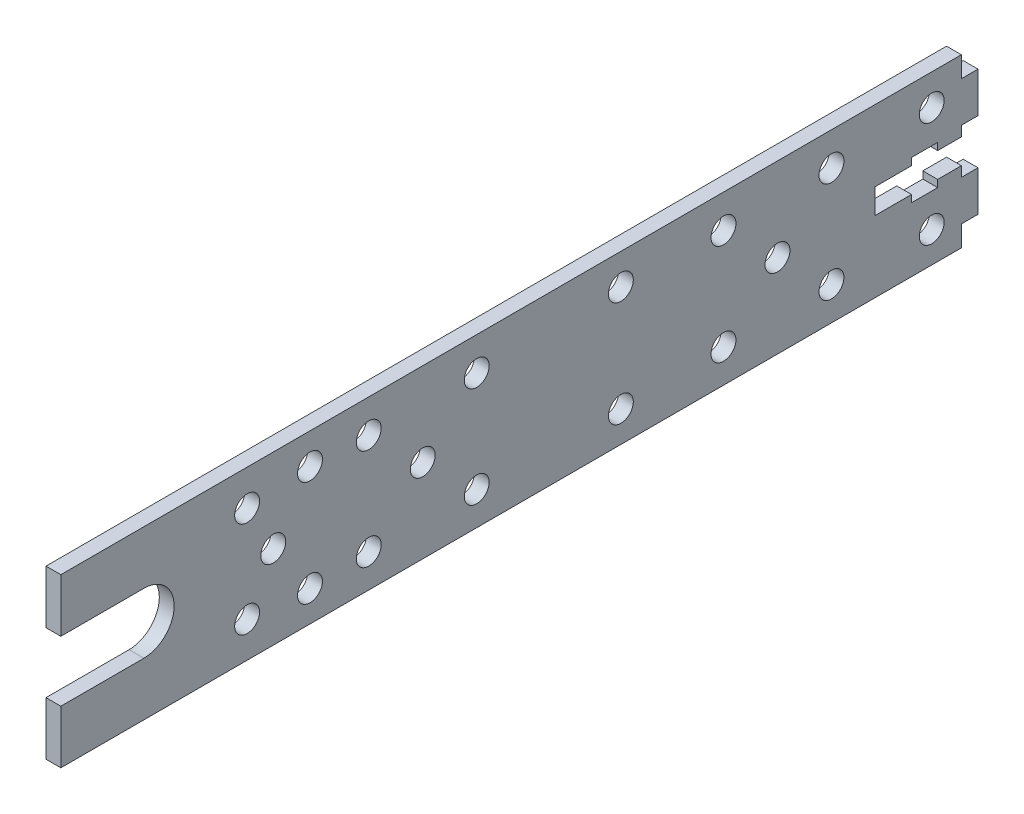
SolidWorks part; units mm, degrees
ref_plane "Front Plane" through (0, 0, 0) normal (0, 0, 1) x (1, 0, 0)
ref_plane "Top Plane" through (0, 0, 0) normal (0, 1, 0) x (1, 0, 0)
ref_plane "Right Plane" through (0, 0, 0) normal (1, 0, 0) x (0, 0, -1)
sketch "Sketch1" plane through (0, 0, 0) normal (1, 0, 0) x (0, 0, -1)
  line L0 (-98.171, 0) -> (98.171, 0) construction
  line L1 (-98.171, 17.907) -> (94.615, 17.907)
  line L2 (-98.171, 17.907) -> (-98.171, 6.477)
  line L3 (-98.171, -17.907) -> (94.615, -17.907)
  line L4 (98.171, 13.462) -> (98.171, 4.826)
  line L5 (94.615, 4.826) -> (94.615, 2.667)
  line L6 (94.615, -2.667) -> (94.615, -4.826)
  line L7 (94.615, 2.667) -> (89.535, 2.667)
  line L8 (94.615, 17.907) -> (94.615, 13.462)
  line L9 (94.615, -2.667) -> (89.535, -2.667)
  line L10 (76.073, 2.667) -> (76.073, -2.667)
  line L11 (86.741, 4.191) -> (86.741, -4.191) construction
  line L12 (-32.258, 10.795) -> (-9.144, 10.795) construction
  line L13 (83.947, 2.667) -> (76.073, 2.667)
  line L14 (89.535, 4.191) -> (83.947, 4.191)
  line L15 (89.535, 4.191) -> (89.535, 2.667)
  line L16 (89.535, -4.191) -> (83.947, -4.191)
  line L17 (83.947, 4.191) -> (83.947, 2.667)
  line L18 (66.802, 10.795) -> (43.688, 10.795) construction
  line L19 (66.802, -10.795) -> (43.688, -10.795) construction
  line L20 (83.947, -2.667) -> (76.073, -2.667)
  line L21 (89.535, -2.667) -> (89.535, -4.191)
  line L22 (83.947, -2.667) -> (83.947, -4.191)
  line L23 (98.171, -4.826) -> (98.171, -13.462)
  line L24 (98.171, 13.462) -> (94.615, 13.462)
  line L25 (98.171, 13.462) -> (98.171, 4.826)
  line L26 (98.171, 4.826) -> (94.615, 4.826)
  line L27 (-32.258, -10.795) -> (-9.144, -10.795) construction
  line L28 (98.171, 13.462) -> (94.615, 4.826) construction
  line L29 (98.171, 4.826) -> (94.615, 13.462) construction
  line L30 (-80.391, 6.477) -> (-98.171, 6.477)
  line L31 (98.171, -4.826) -> (94.615, -4.826)
  line L32 (-20.701, 10.795) -> (-20.701, -10.795) construction
  line L33 (98.171, -13.462) -> (94.615, -4.826) construction
  line L34 (98.171, -4.826) -> (94.615, -13.462) construction
  line L35 (98.171, -13.462) -> (94.615, -13.462)
  line L36 (-80.391, -6.477) -> (-98.171, -6.477)
  line L37 (-98.171, -6.477) -> (-98.171, -17.907)
  line L38 (94.615, -13.462) -> (94.615, -17.907)
  line L39 (55.245, 10.795) -> (55.245, -10.795) construction
  arc A0 (-80.391, -6.477) -> (-80.391, 6.477) centre (-80.391, 0) ccw
  circle A1 centre (-58.293, 10.287) radius 2.667
  circle A2 centre (-58.293, -10.287) radius 2.667
  circle A3 centre (-52.705, 0) radius 2.667
  circle A4 centre (-44.831, 11.303) radius 2.667
  circle A5 centre (21.717, 11.303) radius 2.667
  circle A6 centre (88.265, 11.303) radius 2.667
  circle A7 centre (88.265, -11.303) radius 2.667
  circle A8 centre (21.717, -11.303) radius 2.667
  circle A9 centre (-44.831, -11.303) radius 2.667
  circle A10 centre (-9.144, 10.795) radius 2.667
  circle A11 centre (-32.258, 10.795) radius 2.667
  circle A12 centre (66.802, 10.795) radius 2.667
  circle A13 centre (43.688, 10.795) radius 2.667
  circle A14 centre (43.688, -10.795) radius 2.667
  circle A15 centre (66.802, -10.795) radius 2.667
  circle A16 centre (-32.258, -10.795) radius 2.667
  circle A17 centre (-9.144, -10.795) radius 2.667
  circle A18 centre (-20.701, 0) radius 2.667
  circle A19 centre (55.245, 0) radius 2.667
  point P0 (0, 0)
  point P1 (86.741, 0)
  point P4 (0, 0)
  point P26 (96.393, 9.144)
  point P30 (96.393, -9.144)
  point P44 (76.073, 0)
  dimension "D11" = 12.954
  dimension "D15" = 5.334
  dimension "D26" = 17.78
  dimension "D24" = 39.37
  dimension "D2" = 192.786
  dimension "D3" = 5.334
  dimension "D4" = 18.542
  dimension "D5" = 5.588
  dimension "D6" = 8.636
  dimension "D7" = 8.382
  dimension "D8" = 3.556
  dimension "D9" = 8.636
  dimension "D10" = 9.144
  dimension "D12" = 17.78
  dimension "D13" = 11.43
  dimension "D14" = 11.43
  dimension "D16" = 7.62
  dimension "D17" = 39.878
  dimension "D18" = 150.876
  dimension "D19" = 9.906
  dimension "D20" = 6.604
  dimension "D21" = 76.454
  dimension "D22" = 143.002
  dimension "D23" = 7.112
  dimension "D25" = 115.316
extrude "Boss-Extrude1" add sketch "Sketch1" along normal mid plane 3.175 contours A0 L36 L37 L3 L6 L9 L21 L16 L22 L20 L10 L13 L17 L14 L15 L7 L5 L26 L4 L24 L8 L1 L2 L30 A16 A14 A13 A12 A11 A10 A8 A2 A1 A3 A4 A5 region at (0, 0, -1.0471)
